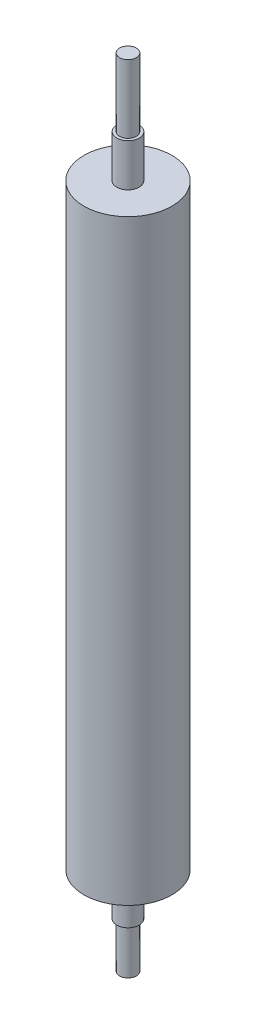
SolidWorks part; units mm, degrees
material "Stainless Steel (ferritic)"
ref_plane "Front Plane" through (0, 0, 0) normal (0, 0, 1) x (1, 0, 0)
ref_plane "Top Plane" through (0, 0, 0) normal (0, 1, 0) x (1, 0, 0)
ref_plane "Right Plane" through (0, 0, 0) normal (1, 0, 0) x (0, 0, -1)
sketch "Sketch1" plane through (0, 0, 0) normal (0, 1, 0) x (1, 0, 0)
  circle A0 centre (0, 0) radius 3.95
  circle A1 centre (0, 0) radius 3.45
  circle A2 centre (0, 0) radius 2.95
  circle A3 centre (0, 0) radius 15.5
  dimension "D1" = 7.9
  dimension "D2" = 6.9
  dimension "D3" = 5.9
  dimension "D4" = 31
extrude "Boss-Extrude8" add sketch "Sketch1" along normal blind 210 contours A3
extrude "Boss-Extrude9" add sketch "Sketch1<9>" against normal blind 15 contours A0
sketch "Sketch1<9>" plane through (0, 0, 0) normal (0, 1, 0) x (1, 0, 0) same geometry as "Sketch1"
extrude "Boss-Extrude10" add sketch "Sketch1<10>" against normal blind 16 from surface contours A2 region at (0, 0, 0) starting at face at (0, -15, 3.95)
sketch "Sketch1<10>" plane through (0, 0, 0) normal (0, 1, 0) x (1, 0, 0) same geometry as "Sketch1"
extrude "Boss-Extrude11" add sketch "Sketch1<11>" along normal blind 15 from surface contours A0 starting at face at (0, 210, 15.5)
sketch "Sketch1<11>" plane through (0, 0, 0) normal (0, 1, 0) x (1, 0, 0) same geometry as "Sketch1"
sketch "Sketch2" plane through (0, 225, 0) normal (0, 1, 0) x (1, 0, 0)
  circle A0 centre (0, 0) radius 2.95
  circle A1 centre (0, 0) radius 3.45
extrude "Boss-Extrude12" add sketch "Sketch2" along normal blind 24 contours A0 region at (0, 225, 0)
